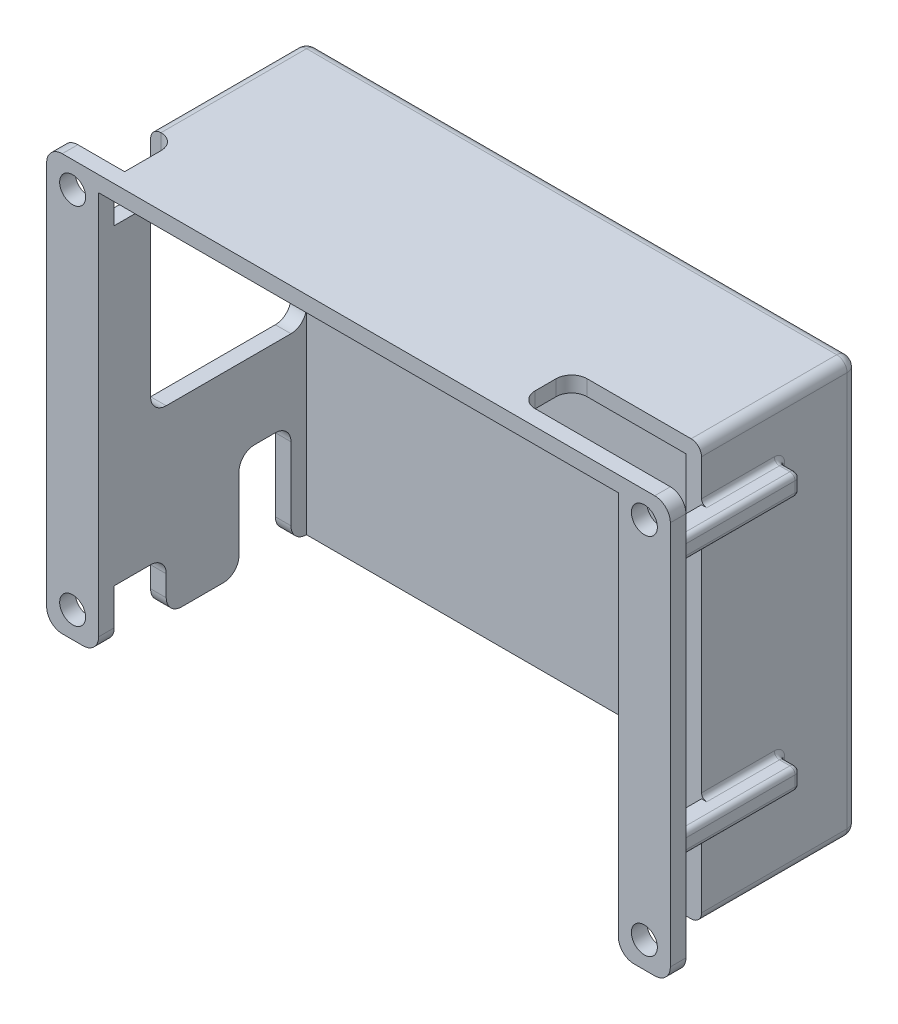
SolidWorks part; units mm, degrees
ref_plane "Front Plane" through (0, 0, 0) normal (0, 0, 1) x (1, 0, 0)
ref_plane "Top Plane" through (0, 0, 0) normal (0, 1, 0) x (1, 0, 0)
ref_plane "Right Plane" through (0, 0, 0) normal (1, 0, 0) x (0, 0, -1)
sketch "Sketch2" plane through (0, 0, 0) normal (0, 0, 1) x (1, 0, 0)
  line L1 (15.306, 62.8336) -> (75.306, 62.8336)
  line L2 (15.306, 62.8336) -> (15.306, 22.8336)
  line L3 (15.306, 22.8336) -> (75.306, 22.8336)
  line L4 (75.306, 62.8336) -> (75.306, 22.8336)
  circle A0 centre (17.806, 60.3336) radius 1.25
  circle A1 centre (17.806, 25.3336) radius 1.25
  circle A2 centre (72.806, 25.3336) radius 1.25
  circle A3 centre (72.806, 60.3336) radius 1.25
  dimension "D2" = 2.5
  dimension "D1" = 60
  dimension "D3" = 40
  dimension "D4" = 2.5
  dimension "D5" = 2.5
  dimension "D6" = 2.5
  dimension "D7" = 2.5
extrude "Boss-Extrude3" add sketch "Sketch2" along normal blind 1.5
sketch "Sketch3" plane through (0, 0, 0) normal (0, 0, -1) x (-1, 0, 0)
  line L0 (-75.306, 62.8336) -> (-15.306, 62.8336) construction
  line L1 (-71.806, 62.8336) -> (-18.806, 62.8336)
  line L2 (-71.806, 62.8336) -> (-71.806, 22.8336)
  line L3 (-71.806, 22.8336) -> (-18.806, 22.8336)
  line L4 (-18.806, 62.8336) -> (-18.806, 22.8336)
  line L6 (-15.306, 22.8336) -> (-75.306, 22.8336) construction
  line L7 (-75.306, 22.8336) -> (-75.306, 62.8336) construction
  line L8 (-15.306, 62.8336) -> (-15.306, 22.8336) construction
  dimension "D1" = 0
  dimension "D2" = 0
  dimension "D3" = 3.5
  dimension "D4" = 3.5
extrude "Boss-Extrude4" add sketch "Sketch3" along normal blind 20
sketch "Sketch7" plane through (0, 0, 1.5) normal (0, 0, 1) x (1, 0, 0)
  line L0 (75.306, 62.8336) -> (15.306, 62.8336) construction
  line L1 (20.306, 61.3336) -> (70.306, 61.3336)
  line L2 (20.306, 61.3336) -> (20.306, 22.8336)
  line L3 (20.306, 22.8336) -> (70.306, 22.8336)
  line L4 (70.306, 61.3336) -> (70.306, 22.8336)
  line L5 (15.306, 62.8336) -> (15.306, 22.8336) construction
  line L6 (75.306, 22.8336) -> (75.306, 62.8336) construction
  line L7 (15.306, 22.8336) -> (75.306, 22.8336) construction
  dimension "D1" = 1.5
  dimension "D2" = 5
  dimension "D3" = 5
  dimension "D4" = 0
extrude "Cut-Extrude4" cut sketch "Sketch7" against normal blind 20
sketch "Sketch8" plane through (71.806, 0, 0) normal (1, 0, 0) x (0, 0, -1)
  line L0 (20, 62.8336) -> (0, 62.8336) construction
  line L1 (0, 62.8336) -> (5, 62.8336)
  line L2 (0, 62.8336) -> (0, 22.8336)
  line L3 (0, 22.8336) -> (5, 22.8336)
  line L4 (5, 62.8336) -> (5, 22.8336)
  line L5 (20, 22.8336) -> (0, 22.8336) construction
  line L6 (0, 24.5836) -> (0, 22.8336) construction
  dimension "D2" = 5
extrude "Cut-Extrude5" cut sketch "Sketch8" against normal blind 12.5
sketch "Sketch11" plane through (18.806, 0, 0) normal (-1, 0, 0) x (0, 0, 1)
  line L1 (0, 62.8336) -> (-5, 62.8336)
  line L2 (0, 62.8336) -> (0, 57.8336)
  line L3 (0, 57.8336) -> (-5, 57.8336)
  line L4 (-5, 62.8336) -> (-5, 57.8336)
  line L5 (0, 22.8336) -> (-5, 22.8336)
  line L6 (0, 22.8336) -> (0, 27.8336)
  line L7 (0, 27.8336) -> (-5, 27.8336)
  line L8 (-5, 22.8336) -> (-5, 27.8336)
  dimension "D1" = 5
  dimension "D2" = 5
extrude "Cut-Extrude8" cut sketch "Sketch11" against normal blind 2.5
sketch "Sketch17" plane through (18.806, 0, 0) normal (-1, 0, 0) x (0, 0, 1)
  line L0 (-20, 22.8336) -> (-20, 62.8336) construction
  line L1 (-18.5, 40.3336) -> (-3.5, 40.3336)
  line L2 (-18.5, 40.3336) -> (-18.5, 57.8336)
  line L3 (-18.5, 57.8336) -> (-3.5, 57.8336)
  line L4 (-3.5, 40.3336) -> (-3.5, 57.8336)
  line L5 (-20, 22.8336) -> (-5, 22.8336) construction
  line L6 (1.5, 62.8336) -> (0, 62.8336) construction
  line L7 (-17, 22.8336) -> (-12, 22.8336)
  line L8 (-17, 22.8336) -> (-17, 32.8336)
  line L9 (-17, 32.8336) -> (-12, 32.8336)
  line L10 (-12, 22.8336) -> (-12, 32.8336)
  dimension "D1" = 5
  dimension "D2" = 17.5
  dimension "D3" = 15
  dimension "D4" = 1.5
  dimension "D5" = 10
  dimension "D6" = 3
  dimension "D7" = 5
extrude "Cut-Extrude13" cut sketch "Sketch17" against normal blind 2.5
sketch "Sketch19" plane through (0, 0, 0) normal (0, 0, -1) x (-1, 0, 0)
  line L0 (-70.306, 61.3336) -> (-70.306, 22.8336) construction
  line L1 (-71.806, 33.3336) -> (-73.806, 33.3336)
  line L2 (-71.806, 33.3336) -> (-71.806, 31.3336)
  line L3 (-71.806, 31.3336) -> (-73.806, 31.3336)
  line L4 (-73.806, 33.3336) -> (-73.806, 31.3336)
  line L5 (-70.306, 22.8336) -> (-75.306, 22.8336) construction
  line L6 (-75.306, 62.8336) -> (-59.306, 62.8336) construction
  line L7 (-71.806, 57.8336) -> (-73.806, 57.8336)
  line L8 (-71.806, 57.8336) -> (-71.806, 55.8336)
  line L9 (-71.806, 55.8336) -> (-73.806, 55.8336)
  line L10 (-73.806, 57.8336) -> (-73.806, 55.8336)
  dimension "D1" = 1.5
  dimension "D2" = 2
  dimension "D3" = 8.5
  dimension "D4" = 2
  dimension "D5" = 5
extrude "Boss-Extrude5" add sketch "Sketch19" along normal blind 12.5
fillet "Fillet1" radius 1.5 6 edges at (70.306, 22.8336, 0.75) (15.306, 62.8336, 0.75) (75.306, 62.8336, 0.75) (75.306, 22.8336, 0.75) (15.306, 22.8336, 0.75) (20.306, 22.8336, 0.75)
fillet "Fillet2" radius 1.5 13 edges at (59.306, 62.0836, -5) (59.306, 62.0836, 0) (19.556, 40.3336, -3.5) (19.556, 40.3336, -18.5) (19.556, 57.8336, -3.5) (19.556, 57.8336, -5) (19.556, 57.8336, -18.5) (19.556, 32.8336, -12) (19.556, 22.8336, -12) (19.556, 22.8336, -5) (19.556, 27.8336, -5) (19.556, 32.8336, -17) (19.556, 22.8336, -17)
fillet "Fillet3" radius 1 7 edges at (71.806, 62.8336, -12.5) (71.806, 22.8336, -12.5) (18.806, 62.8336, -12.5) (71.806, 42.8336, -20) (45.306, 22.8336, -20) (18.806, 42.8336, -20) (45.306, 62.8336, -20)
fillet "Fillet4" radius 0.5 24 edges at (72.806, 55.8336, 0) (72.806, 33.3336, 0) (72.806, 31.3336, 0) (73.806, 56.8336, 0) (71.806, 32.3336, 0) (73.806, 32.3336, 0) (71.806, 56.8336, 0) (72.806, 57.8336, 0) (71.806, 32.3336, -12.5) (71.806, 56.8336, -12.5) (71.806, 33.3336, -8.75) (71.806, 57.8336, -8.75) (71.806, 55.8336, -8.75) (73.806, 57.8336, -6.25) (73.806, 33.3336, -6.25) (71.806, 31.3336, -8.75) (73.806, 31.3336, -6.25) (73.806, 55.8336, -6.25) (72.806, 55.8336, -12.5) (73.806, 56.8336, -12.5) (72.806, 57.8336, -12.5) (72.806, 31.3336, -12.5) (73.806, 32.3336, -12.5) (72.806, 33.3336, -12.5)
fillet "Fillet5" radius 1.5 1 edges at (21.306, 62.0836, -5)
